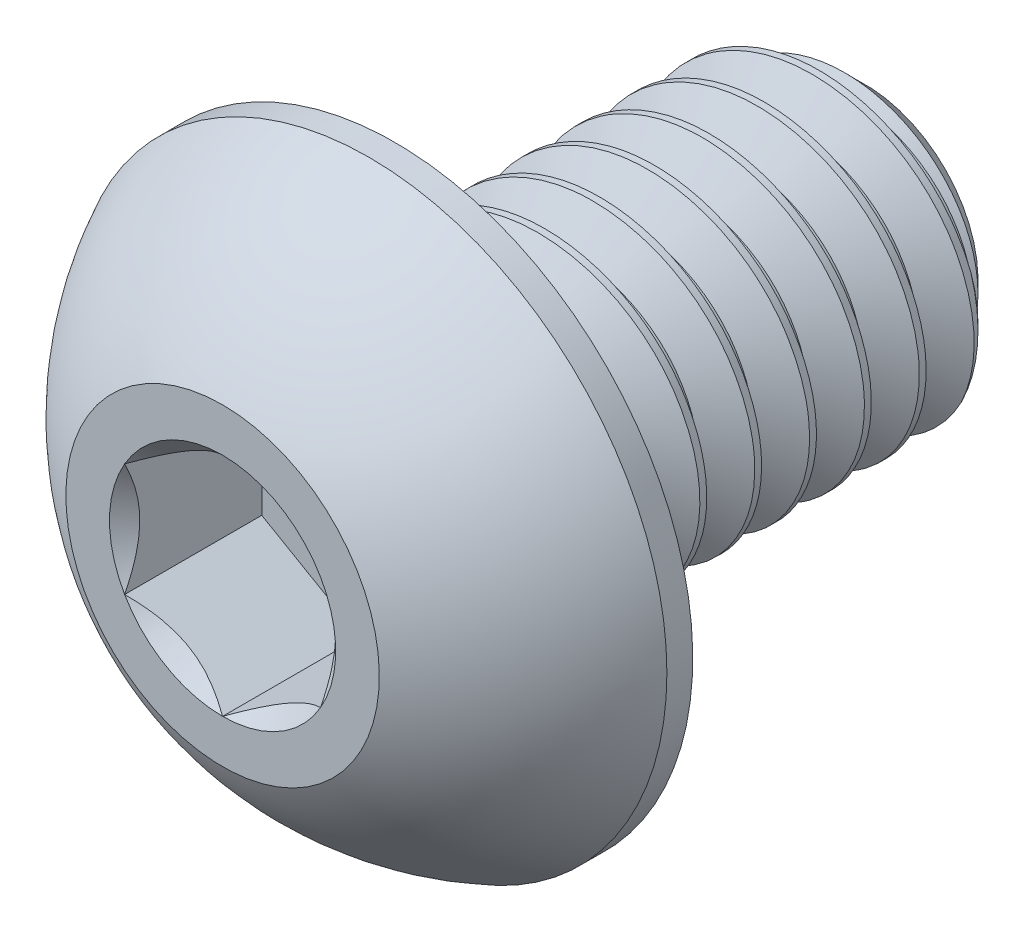
SolidWorks part; units mm, degrees
ref_plane "Front Plane" through (0, 0, 0) normal (0, 0, 1) x (1, 0, 0)
ref_plane "Top Plane" through (0, 0, 0) normal (0, 1, 0) x (1, 0, 0)
ref_plane "Right Plane" through (0, 0, 0) normal (1, 0, 0) x (0, 0, -1)
sketch "Sketch1" plane through (0, 0, 0) normal (1, 0, 0) x (0, 0, -1)
  line L0 (-4.1, 0) -> (4.1, 0) construction
  line L1 (-1.9, 3.8) -> (-1.9, -3.8) construction
  line L2 (4.1, 2) -> (4.1, -2) construction
  line L3 (4.0563, 2.0758) -> (4.4063, 1.4696) construction
  line L4 (4.4063, 1.4696) -> (4.7562, 2.0758) construction
  line L5 (4.7562, 2.0758) -> (4.0563, 2.0758) construction
  line L6 (4.1, 2) -> (4.7125, 2) construction
  line L7 (4.4062, 2.0758) -> (4.4062, 2) construction
  line L8 (4.4062, 2) -> (4.4062, 1.5453) construction
  line L9 (4.4062, 1.5453) -> (4.4063, 1.4696) construction
  line L10 (4.3625, 1.5453) -> (4.45, 1.5453)
  line L11 (4.0781, 2.0379) -> (4.7344, 2.0379)
  line L12 (4.45, 1.5453) -> (4.7344, 2.0379)
  line L13 (4.3625, 1.5453) -> (4.0781, 2.0379)
  line L14 (-4.1, 1.25) -> (-4.1, -1.25) construction
  line L15 (4.1, 2) -> (-1.9, 2) construction
  point P3 (-1.9, 0)
  point P6 (-2.35, 0)
  point P21 (4.4062, 2.0379)
  point P24 (-2.23, 3.8)
  point P25 (2.35, -2)
  point P26 (-4.1, 2)
  dimension "Head Height" = 2.2
  dimension "Length" = 6
  dimension "Head Dia" = 7.6
  dimension "Thread Dia" = 4
  dimension "Pitch" = 0.7
  dimension "Drive Size" = 2.5
  dimension "D1" = 1.75
  dimension "D4" = 1.75
sketch "Sketch2" plane through (0, 0, 0) normal (1, 0, 0) x (0, 0, -1)
  line L0 (-4.1, 0) -> (4.1, 0)
  line L1 (4.1, 0) -> (4.1, 1.44)
  line L2 (4.1, 2) -> (4.1, -2) construction
  line L3 (4.1, 1.44) -> (3.54, 2)
  line L4 (3.54, 2) -> (-1.9, 2)
  line L5 (-1.9, 3.8) -> (-1.9, -3.8) construction
  line L6 (-1.9, 2) -> (-1.9, 3.8)
  line L7 (-1.9, 3.8) -> (-2.23, 3.8)
  line L8 (4.1, 2) -> (4.7125, 2) construction
  line L9 (-4.1, 0) -> (-4.1, 2)
  arc A0 (-4.1, 2) -> (-2.23, 3.8) centre (-0.3736, 0) cw
  dimension "D1" = 0.56
  dimension "D2" = 45
revolve "Revolve1" add sketch "Sketch2" angle 360 about L0
sketch "Sketch3" plane through (0, 0, 4.1) normal (0, 0, 1) x (1, 0, 0)
  line L1 (0, 1.4434) -> (-1.25, 0.7217)
  line L2 (-1.25, 0.7217) -> (-1.25, -0.7217)
  line L3 (-1.25, -0.7217) -> (0, -1.4434)
  line L4 (0, -1.4434) -> (1.25, -0.7217)
  line L5 (1.25, -0.7217) -> (1.25, 0.7217)
  line L6 (1.25, 0.7217) -> (0, 1.4434)
  circle A0 centre (0, 0) radius 1.25 construction
  dimension "D1" = 2.5
extrude "Cut-Extrude1" cut sketch "Sketch3" against normal up to vertex (1.75 mm away) up to point (0, 0, 2.35)
sketch "Sketch4" plane through (0, 0, 4.1) normal (0, 0, 1) x (1, 0, 0)
  circle A0 centre (0, 0) radius 1.4434
extrude "Cut-Extrude2" cut sketch "Sketch4" against normal blind 10 draft 45
split "Split1" bodies to split 106 resulting bodies 107 108 split by face at (0, -3.8, 1.9)
sketch "Sketch5" plane through (0, 0, -4.1) normal (0, 0, -1) x (-1, 0, 0)
  circle A0 centre (0, 0) radius 2 construction
  circle A1 centre (0, 0) radius 2
curve "Helix/Spiral1" pitch 0.7 height 6.7 radius 2 centre (0, 0, -4.1) axis (0, 0, 1) start towards (0, 1, 0)
sketch "Sketch6" plane through (0, 0, 0) normal (1, 0, 0) x (0, 0, -1)
  line L0 (4.3625, 1.5453) -> (4.45, 1.5453) construction
  line L1 (4.3625, 1.5453) -> (4.0781, 2.0379) construction
  line L2 (4.0781, 2.0379) -> (4.7344, 2.0379) construction
  line L3 (4.45, 1.5453) -> (4.7344, 2.0379) construction
  line L4 (4.3625, 1.5453) -> (4.45, 1.5453)
  line L5 (4.3625, 1.5453) -> (4.0781, 2.0379)
  line L6 (4.0781, 2.0379) -> (4.7344, 2.0379)
  line L7 (4.45, 1.5453) -> (4.7344, 2.0379)
sweep "Cut-Sweep1" cut profiles "Sketch6" path "Helix/Spiral1" align with end faces yes
sketch "Sketch7" plane through (0, 0, 1.9) normal (0, 0, -1) x (-1, 0, 0)
  circle A1 centre (0, 0) radius 2
  circle A2 centre (0, 0) radius 2
  dimension "D1" = 0
extrude "Boss-Extrude1" add sketch "Sketch7" along normal blind 10 draft 30
equation "\"D2@Sketch1\" = \"Pitch@Sketch1\" / 8"
equation "\"D1@Sketch1\"=\"Drive Size@Sketch1\"*.7"
equation "\"D3@Sketch1\"=\"Head Height@Sketch1\"*.15"
equation "\"D1@Sketch2\"=\"Pitch@Sketch1\"*.8"
equation "\"D1@Sketch3\"=\"Drive Size@Sketch1\""
equation "\"D4@Helix/Spiral1\"=\"Pitch@Sketch1\""
equation "\"D3@Helix/Spiral1\"=\"Length@Sketch1\"+\"Pitch@Sketch1\""
equation "\"D4@Sketch1\"=\"Pitch@Sketch1\"*2.5"
